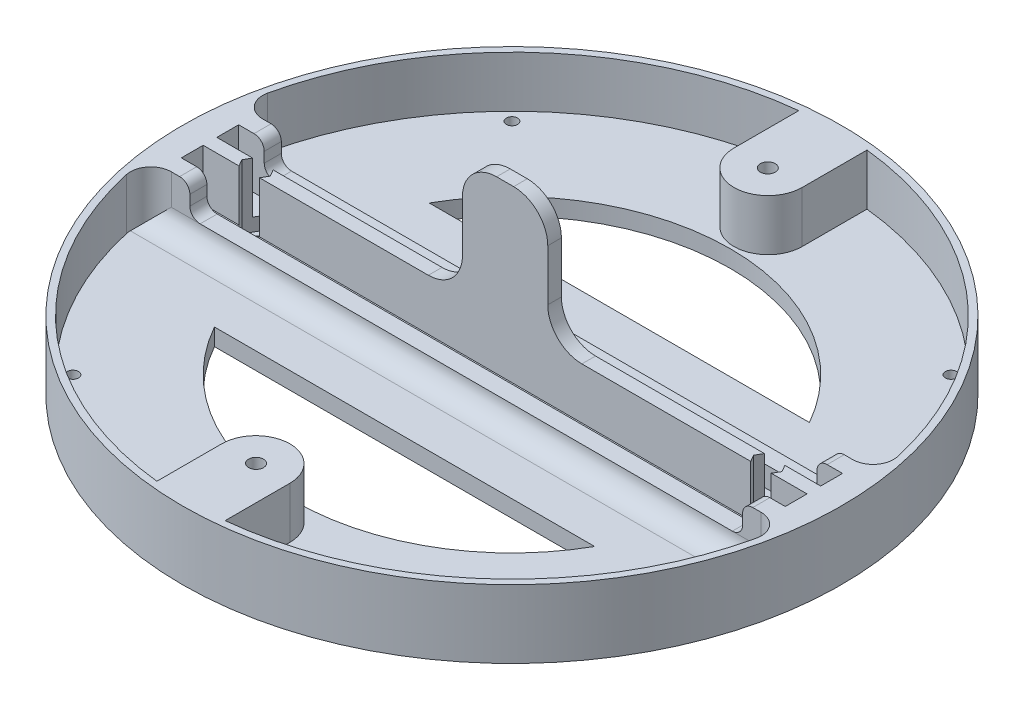
SolidWorks part; units mm, degrees
ref_plane "Front Plane" through (0, 0, 0) normal (0, 0, 1) x (1, 0, 0)
ref_plane "Top Plane" through (0, 0, 0) normal (0, 1, 0) x (1, 0, 0)
ref_plane "Right Plane" through (0, 0, 0) normal (1, 0, 0) x (0, 0, -1)
sketch "Sketch1" plane through (0, 0, 0) normal (0, 1, 0) x (1, 0, 0)
  circle A0 centre (0, 0) radius 96.6
  dimension "D1" = 193.2
extrude "Boss-Extrude1" add sketch "Sketch1" along normal blind 5
sketch "Sketch4" plane through (0, 5, 0) normal (0, 1, 0) x (1, 0, 0)
  circle A0 centre (0, 0) radius 96.6
  circle A1 centre (0, 0) radius 94.6
  dimension "D1" = 193.2
  dimension "D2" = 189.2
extrude "Boss-Extrude3" add sketch "Sketch4" along normal blind 15
sketch "Sketch5" plane through (0, 5, 0) normal (0, 1, 0) x (1, 0, 0)
  line L0 (-94.6, 0) -> (94.6, 0)
  line L1 (-88.5, -2) -> (88.5, -2)
  line L2 (-88.5, -2) -> (-88.5, -8.4)
  line L3 (-88.5, -8.4) -> (88.5, -8.4)
  line L4 (88.5, -2) -> (88.5, -8.4)
  line L5 (-88.5, -2) -> (88.5, -8.4) construction
  line L6 (-88.5, -8.4) -> (88.5, -2) construction
  line L7 (-94.6, 0) -> (-94.6, -13.4)
  line L8 (-94.6, -13.4) -> (94.6, -13.4)
  line L9 (94.6, -13.4) -> (94.6, 0)
  circle A0 centre (0, 0) radius 94.6 construction
  circle A1 centre (0, 0) radius 94.6 construction
  point P0 (0, -5.2)
  dimension "D1" = 2
  dimension "D2" = 177
  dimension "D3" = 6.4
  dimension "D4" = 5
extrude "Boss-Extrude4" add sketch "Sketch5" along normal blind 15
mirror "Mirror1" about plane through (0, 0, 0) normal (0, 0, 1) of "Boss-Extrude4"
sketch "Sketch6" plane through (0, 0, 0) normal (0, -1, 0) x (1, 0, 0)
  circle A0 centre (0, 0) radius 22.5
  dimension "D1" = 45
extrude "Cut-Extrude1" cut sketch "Sketch6" against normal blind 4
sketch "Sketch7" plane through (0, 20, 0) normal (0, 1, 0) x (1, 0, 0)
  line L0 (93.6461, -13.4) -> (-93.6461, -13.4) construction
  line L1 (0, -13.4) -> (-81, -13.4)
  line L3 (0, -8.4) -> (-81, -8.4)
  line L4 (-81, -13.4) -> (-81, -8.4)
  line L5 (-88.5, -8.4) -> (88.5, -8.4) construction
  line L7 (0, -13.4) -> (81, -13.4)
  line L9 (0, -8.4) -> (81, -8.4)
  line L10 (81, -13.4) -> (81, -8.4)
  dimension "D1" = 81
  dimension "D2" = 81
extrude "Cut-Extrude2" cut sketch "Sketch7" against normal blind 9
mirror "Mirror2" about plane through (0, 0, 0) normal (0, 0, 1) of "Cut-Extrude2"
sketch "Sketch10" plane through (0, 5, 0) normal (0, 1, 0) x (1, 0, 0)
  line L0 (0, -13.4) -> (0, -94.6) construction
  line L1 (93.6461, -13.4) -> (-93.6461, -13.4) construction
  line L2 (-10, -75.0738) -> (-10, -95.0738)
  line L3 (-10, -95.0738) -> (10, -95.0738)
  line L4 (10, -95.0738) -> (10, -75.0738)
  arc A0 (-93.6461, -13.4) -> (93.6461, -13.4) centre (0, 0) ccw construction
  arc A1 (10, -75.0738) -> (-10, -75.0738) centre (0, -75.0738) ccw
  dimension "D1" = 20
  dimension "D2" = 20
extrude "Boss-Extrude6" add sketch "Sketch10" along normal up to surface (15 mm away) up to face at (0, 20, 17.24)
mirror "Mirror3" about plane through (0, 0, 0) normal (0, 0, 1) of "Boss-Extrude6"
sketch "Sketch8" plane through (0, 0, 0) normal (0, -1, 0) x (1, 0, 0)
  circle A0 centre (-75, 0) radius 2.175
  circle A1 centre (0, 75) radius 2.175
  circle A2 centre (75, 0) radius 2.175
  circle A3 centre (0, -75) radius 2.175
  point P12 (0, 0)
  dimension "D1" = 4.35
  dimension "D2" = 75
  dimension "D3" = 4
extrude "Cut-Extrude4" cut sketch "Sketch8" against normal blind 29
sketch "Sketch25" plane through (0, 20, 0) normal (0, 1, 0) x (1, 0, 0)
  line L0 (70.8431, 0) -> (72.9215, -3.6)
  line L1 (-70.8431, 0) -> (-72.9215, 3.6)
  line L2 (-72.9215, 3.6) -> (-77.0785, 3.6)
  line L3 (-77.0785, 3.6) -> (-79.1569, 0)
  line L4 (-79.1569, 0) -> (-77.0785, -3.6)
  line L5 (-77.0785, -3.6) -> (-72.9215, -3.6)
  line L6 (-72.9215, -3.6) -> (-70.8431, 0)
  line L7 (72.9215, -3.6) -> (77.0785, -3.6)
  line L8 (77.0785, -3.6) -> (79.1569, 0)
  line L9 (79.1569, 0) -> (77.0785, 3.6)
  line L10 (77.0785, 3.6) -> (72.9215, 3.6)
  line L11 (72.9215, 3.6) -> (70.8431, 0)
  circle A0 centre (-75, 0) radius 3.6 construction
  circle A1 centre (75, 0) radius 3.6 construction
  point P20 (0, 0)
  dimension "D1" = 7.2
  dimension "D2" = 2
sketch "Sketch19" plane through (0, 5, 0) normal (0, 1, 0) x (1, 0, 0)
  line L0 (-55.7254, -31.4751) -> (55.7254, -31.4751)
  arc A0 (-55.7254, -31.4751) -> (55.7254, -31.4751) centre (0, 0) ccw
extrude "Cut-Extrude9" cut sketch "Sketch19" against normal blind 30
mirror "Mirror4" about plane through (0, 0, 0) normal (0, 0, 1) of "Cut-Extrude9"
fillet "Fillet3" radius 3 8 edges at (-81, 11, 10.9) (-81, 11, -10.9) (81, 11, -10.9) (81, 11, 10.9) (81, 20, 10.9) (81, 20, -10.9) (-81, 20, -10.9) (-81, 20, 10.9)
sketch "Sketch20" plane through (0, 0, 0) normal (0, -1, 0) x (1, 0, 0)
  line L0 (0, 0) -> (-64.3467, 64.3467) construction
  line L1 (0, 0) -> (-119.5015, 0) construction
  circle A0 centre (-64.3467, 64.3467) radius 1.65
  circle A1 centre (64.3467, 64.3467) radius 1.65
  circle A2 centre (64.3467, -64.3467) radius 1.65
  circle A3 centre (-64.3467, -64.3467) radius 1.65
  point P14 (0, 0)
  dimension "D3" = 3.3
  dimension "D1" = 45
  dimension "D2" = 91
  dimension "D4" = 4
extrude "Cut-Extrude10" cut sketch "Sketch20" against normal blind 10
sketch "Sketch24" plane through (0, 20, 0) normal (0, 1, 0) x (1, 0, 0)
  line L0 (88.5, 2) -> (75.8548, 2) construction
  line L1 (-12.5, -2) -> (12.5, -2)
  line L2 (-12.5, -2) -> (-12.5, 2)
  line L3 (-12.5, 2) -> (12.5, 2)
  line L4 (12.5, -2) -> (12.5, 2)
  line L5 (-12.5, -2) -> (12.5, 2) construction
  line L6 (-12.5, 2) -> (12.5, -2) construction
  point P1 (0, 0)
  dimension "D1" = 25
extrude "Boss-Extrude8" add sketch "Sketch24" along normal blind 35
fillet "Fillet2" radius 10 4 edges at (-12.5, 20, 0) (-12.5, 55, 0) (12.5, 55, 0) (12.5, 20, 0)
extrude "Cut-Extrude11" cut sketch "Sketch25" against normal blind 18.8
fillet "Fillet4" radius 6 6 edges at (93.6461, 12.5, -13.4) (0, 5, -13.4) (-93.6461, 12.5, -13.4) (93.6461, 12.5, 13.4) (-93.6461, 12.5, 13.4) (0, 5, 13.4)
